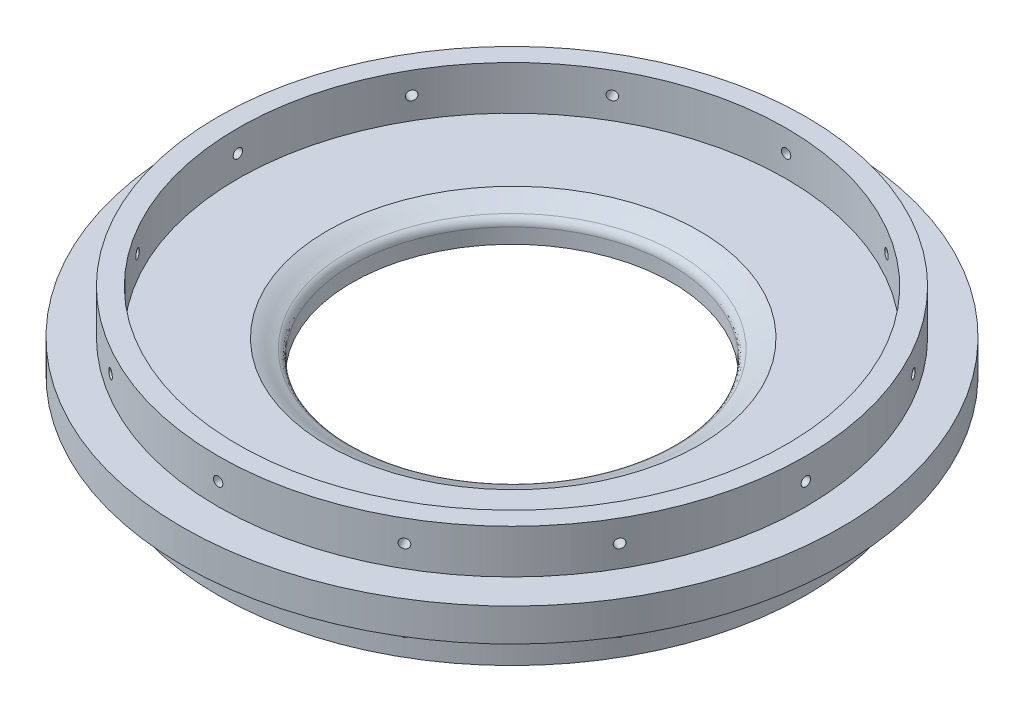
SolidWorks part; units mm, degrees
material "6061-T6 (SS)"
ref_plane "Front Plane" through (0, 0, 0) normal (0, 0, 1) x (1, 0, 0)
ref_plane "Top Plane" through (0, 0, 0) normal (0, 1, 0) x (1, 0, 0)
ref_plane "Right Plane" through (0, 0, 0) normal (1, 0, 0) x (0, 0, -1)
sketch "Sketch1" plane through (0, 0, 0) normal (0, 1, 0) x (1, 0, 0)
  line L5 (0, 0) -> (127.635, 0)
  line L6 (0, 0) -> (0, 127.635)
  line L7 (0, 127.635) -> (127.635, 127.635)
  line L8 (127.635, 0) -> (127.635, 127.635)
  dimension "D1" = 127.635
  dimension "D2" = 127.635
extrude "Boss-Extrude1" add sketch "Sketch1" along normal blind 9.525 contours L5 L8 L7 L6
sketch "Sketch12" plane through (0, 0, 0) normal (0, -1, 0) x (1, 0, 0)
  line L0 (63.8175, 0) -> (63.8175, -127.635) construction
  line L1 (0, 0) -> (127.635, 0) construction
  line L2 (0, -127.635) -> (127.635, -127.635) construction
  line L3 (0, -63.8175) -> (127.635, -63.8175) construction
  line L4 (0, 0) -> (0, -127.635) construction
  line L5 (127.635, 0) -> (127.635, -127.635) construction
  circle A0 centre (63.8175, -63.8175) radius 95.4151
  dimension "D1" = 190.8302
extrude "Boss-Extrude2" add sketch "Sketch12" against normal up to surface (9.525 mm away) contours A0 up to face at (63.8175, 9.525, -63.8175)
sketch "Sketch5" plane through (0, 9.525, 0) normal (0, 1, 0) x (1, 0, 0)
  circle A0 centre (63.8175, 63.8175) radius 46.355
  circle A3 centre (63.8175, 63.8175) radius 95.4151 construction
  dimension "D1" = 92.71
extrude "Cut-Extrude1" cut sketch "Sketch5" against normal blind 9.525
sketch "Sketch14" plane through (0, 9.525, 0) normal (0, -1, 0) x (1, 0, 0)
  line L0 (63.8175, -63.8175) -> (147.6375, -63.8175) construction
  line L1 (0, -19.2087) -> (0, 19.2087) construction
  line L2 (147.6375, -63.8175) -> (152.7175, -63.8175)
  line L3 (136.3808, -105.7742) -> (140.8401, -108.2104)
  circle A0 centre (63.8175, -63.8175) radius 46.355 construction
  arc A2 (147.6375, -63.8175) -> (136.3808, -105.7742) centre (63.8175, -63.8175) cw
  arc A3 (152.7175, -63.8175) -> (140.8401, -108.2104) centre (63.8175, -63.8175) cw
  point P0 (63.8175, -63.8175)
  dimension "D1" = 83.82
  dimension "D2" = 88.9
  dimension "D3" = 46.482
  dimension "D4" = 43.942
ref_plane "Support mirror reference plane" through (0, 4.7625, 0) normal (0, 1, 0) x (1, 0, 0)
sketch "Sketch25" plane through (0, 9.525, 0) normal (0, -1, 0) x (1, 0, 0)
  line L0 (63.8175, -63.8175) -> (123.0872, -4.5478) construction
  line L2 (123.0872, -4.5478) -> (126.6793, -0.9557)
  line L3 (144.7953, -42.1754) -> (149.6712, -40.7448)
  line L5 (63.8175, -63.8175) -> (147.6375, -63.8175) construction
  arc A2 (123.0872, -4.5478) -> (144.7953, -42.1754) centre (63.8175, -63.8175) cw
  arc A3 (126.6793, -0.9557) -> (149.6712, -40.7448) centre (63.8175, -63.8175) cw
  point P0 (63.8175, -63.8175)
  dimension "D1" = 83.82
  dimension "D2" = 88.9
  dimension "D3" = 46.482
  dimension "D4" = 43.942
  dimension "D5" = 45
sketch "Sketch30" plane through (0, 0, 0) normal (0, -1, 0) x (1, 0, 0)
  circle A0 centre (63.8175, -63.8175) radius 85.09
  circle A1 centre (63.8175, -63.8175) radius 79.375
  dimension "D1" = 170.18
  dimension "D2" = 158.75
extrude "Boss-Extrude3" add sketch "Sketch30" along normal blind 12.7
mirror "Mirror1" about plane through (0, 4.7625, 0) normal (0, 1, 0) of "Boss-Extrude3"
sketch "Sketch31" plane through (0, 0, 0) normal (0, -1, 0) x (-1, 0, 0)
  line L0 (-63.8175, -52.481) -> (-63.8175, 177.7216) construction
ref_plane "Plane1" through (0, 0, -148.9075) normal (0, 0, -1) x (-1, 0, 0)
ref_plane "Plane2" through (63.8175, 0, 0) normal (-1, 0, 0) x (0, 0, -1)
sketch "Sketch32" plane through (0, 0, -148.9075) normal (0, 0, -1) x (-1, 0, 0)
  line L4 (-63.8175, -87.3125) -> (-63.8175, 87.3125) construction
  line L5 (-148.9075, 0) -> (21.2725, 0) construction
  line L6 (21.2725, 9.525) -> (-148.9075, 9.525) construction
  circle A0 centre (-63.8175, -6.35) radius 1.3526
  circle A1 centre (-63.8175, 15.875) radius 1.3525
  dimension "D1" = 2.7051
  dimension "D2" = 2.7051
  dimension "D3" = 6.35
  dimension "D4" = 6.35
extrude "Cut-Extrude4" cut sketch "Sketch32" against normal blind 15.24
pattern_circular "CirPattern2" count 12 over 360 about axis through (63.8175, -12.7, -63.8175) along (0, 1, 0) of "Cut-Extrude4"
ref_plane "Plane3" through (0, 0, -63.754) normal (0, 0, 1) x (1, 0, 0)
sketch "Sketch35" plane through (0, 0, -63.754) normal (0, 0, 1) x (1, 0, 0)
  line L1 (118.0423, 9.525) -> (109.7873, 9.525)
  line L3 (110.1725, 9.525) -> (17.4625, 9.525) construction
  line L4 (17.4625, 0) -> (110.1725, 0) construction
  line L5 (17.4625, 0) -> (110.1725, 0)
  line L6 (64.2379, -16.1799) -> (64.2379, 15.7632) construction
  line L7 (109.7873, 9.525) -> (109.7873, 5.81)
  spline S0 degree 3 poles (118.0423, 9.525) (115.2087, 8.4474) (112.8295, 6.3493) (109.7873, 5.81) knots 0 0 0 0 1 1 1 1
  point P1 (112.1182, 6.5325)
  point P10 (113.6399, 7.5942)
  point P11 (115.3935, 8.8163)
  point P12 (116.6819, 8.9248)
  dimension "D2" = 8.255
revolve "Cut-Revolve1" cut sketch "Sketch35" angle 360 about L6 region at (112.545, 8.1821, -63.754)
fillet "Fillet2" radius 2.54 1 edges at (74.4801, 5.9826, -108.9295)
